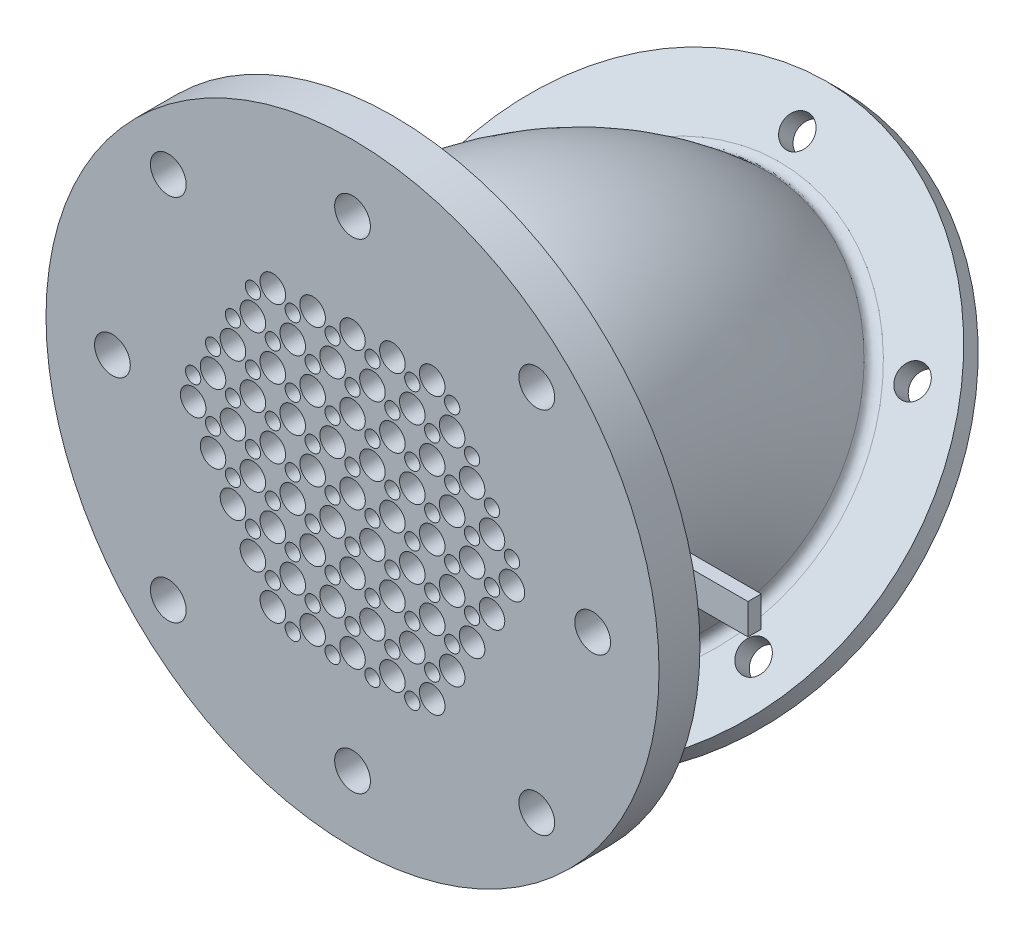
SolidWorks part; units mm, degrees
ref_plane "Спереди" through (0, 0, 0) normal (0, 0, 1) x (1, 0, 0)
ref_plane "Сверху" through (0, 0, 0) normal (0, 1, 0) x (1, 0, 0)
ref_plane "Справа" through (0, 0, 0) normal (1, 0, 0) x (0, 0, -1)
sketch "Sketch1" plane through (0, 0, 0) normal (0, 0, 1) x (1, 0, 0)
  line L0 (3.9, 6.755) -> (7.8, 0) construction
  line L2 (5.85, 10.1325) -> (11.7, 0) construction
  line L4 (7.8, 13.51) -> (15.6, 0) construction
  circle A61 centre (0, 0) radius 18.6468
  circle A131 centre (0, 0) radius 1.25
  circle A484 centre (3.9, 0) radius 1.25
  circle A485 centre (7.8, 0) radius 1.25
  circle A486 centre (11.7, 0) radius 1.25
  circle A487 centre (15.6, 0) radius 1.25
  circle A488 centre (1.95, -3.3775) radius 1.25
  circle A489 centre (3.9, -6.755) radius 1.25
  circle A490 centre (5.85, -10.1325) radius 1.25
  circle A491 centre (7.8, -13.51) radius 1.25
  circle A492 centre (-1.95, -3.3775) radius 1.25
  circle A493 centre (-3.9, -6.755) radius 1.25
  circle A494 centre (-5.85, -10.1325) radius 1.25
  circle A495 centre (-7.8, -13.51) radius 1.25
  circle A496 centre (-3.9, 0) radius 1.25
  circle A497 centre (-7.8, 0) radius 1.25
  circle A498 centre (-11.7, 0) radius 1.25
  circle A499 centre (-15.6, 0) radius 1.25
  circle A500 centre (-1.95, 3.3775) radius 1.25
  circle A501 centre (-3.9, 6.755) radius 1.25
  circle A502 centre (-5.85, 10.1325) radius 1.25
  circle A503 centre (-7.8, 13.51) radius 1.25
  circle A504 centre (1.95, 3.3775) radius 1.25
  circle A505 centre (3.9, 6.755) radius 1.25
  circle A506 centre (5.85, 10.1325) radius 1.25
  circle A507 centre (7.8, 13.51) radius 1.25
  circle A508 centre (5.85, 3.3775) radius 1.25
  circle A509 centre (7.8, 6.755) radius 1.25
  circle A510 centre (9.75, 3.3775) radius 1.25
  circle A511 centre (11.7, 6.755) radius 1.25
  circle A512 centre (9.7491, 10.1341) radius 1.25
  circle A513 centre (13.6509, 3.3759) radius 1.25
  circle A514 centre (5.85, -3.3791) radius 1.25
  circle A515 centre (9.75, -3.3791) radius 1.25
  circle A516 centre (7.8, -6.7566) radius 1.25
  circle A517 centre (11.7, -6.7566) radius 1.25
  circle A518 centre (9.7491, -10.1356) radius 1.25
  circle A519 centre (13.6509, -3.3775) radius 1.25
  circle A520 centre (-0.0013, -6.7573) radius 1.25
  circle A521 centre (1.9487, -10.1348) radius 1.25
  circle A522 centre (-1.9513, -10.1348) radius 1.25
  circle A523 centre (-0.0013, -13.5123) radius 1.25
  circle A524 centre (-3.9032, -13.5123) radius 1.25
  circle A525 centre (3.9005, -13.5123) radius 1.25
  circle A526 centre (-5.8527, -3.3791) radius 1.25
  circle A527 centre (-7.8027, -6.7566) radius 1.25
  circle A528 centre (-9.7527, -3.3791) radius 1.25
  circle A529 centre (-11.7027, -6.7566) radius 1.25
  circle A530 centre (-13.6536, -3.3775) radius 1.25
  circle A531 centre (-9.7518, -10.1356) radius 1.25
  circle A532 centre (-5.8527, 3.3775) radius 1.25
  circle A533 centre (-9.7527, 3.3775) radius 1.25
  circle A534 centre (-7.8027, 6.755) radius 1.25
  circle A535 centre (-11.7027, 6.755) radius 1.25
  circle A536 centre (-9.7518, 10.1341) radius 1.25
  circle A537 centre (-13.6536, 3.3759) radius 1.25
  circle A538 centre (-0.0014, 6.7558) radius 1.25
  circle A539 centre (-1.9514, 10.1333) radius 1.25
  circle A540 centre (1.9486, 10.1333) radius 1.25
  circle A541 centre (-0.0014, 13.5108) radius 1.25
  circle A542 centre (3.9005, 13.5108) radius 1.25
  circle A543 centre (-3.9032, 13.5108) radius 1.25
  circle A544 centre (13.65, -1.1258) radius 2.2517 construction
  circle A545 centre (11.7009, -4.5044) radius 2.2522 construction
  circle A546 centre (9.75, -7.8834) radius 2.2522 construction
  circle A547 centre (7.7987, -11.2591) radius 2.2509 construction
  circle A548 centre (13.65, -1.1258) radius 0.75
  circle A549 centre (11.7009, -4.5044) radius 0.75
  circle A550 centre (9.75, -7.8834) radius 0.75
  circle A551 centre (7.7987, -11.2591) radius 0.75
  circle A552 centre (9.75, -1.1258) radius 0.75
  circle A553 centre (7.8009, -4.5044) radius 0.75
  circle A554 centre (5.85, -7.8834) radius 0.75
  circle A555 centre (3.8987, -11.2591) radius 0.75
  circle A556 centre (5.85, -1.1258) radius 0.75
  circle A557 centre (3.9009, -4.5044) radius 0.75
  circle A558 centre (1.95, -7.8834) radius 0.75
  circle A559 centre (-0.0013, -11.2591) radius 0.75
  circle A560 centre (1.95, -1.1258) radius 0.75
  circle A561 centre (0.0009, -4.5044) radius 0.75
  circle A562 centre (-1.95, -7.8834) radius 0.75
  circle A563 centre (-3.9013, -11.2591) radius 0.75
  circle A564 centre (-1.95, -1.1258) radius 0.75
  circle A565 centre (-3.8991, -4.5044) radius 0.75
  circle A566 centre (-5.85, -7.8834) radius 0.75
  circle A567 centre (-7.8013, -11.2591) radius 0.75
  circle A568 centre (-5.85, -1.1258) radius 0.75
  circle A569 centre (-7.7991, -4.5044) radius 0.75
  circle A570 centre (-9.75, -7.8834) radius 0.75
  circle A572 centre (-9.75, -1.1258) radius 0.75
  circle A573 centre (-11.6991, -4.5044) radius 0.75
  circle A576 centre (-13.65, -1.1258) radius 0.75
  circle A580 centre (-15.5991, -4.5044) radius 0.75
  circle A581 centre (-13.65, -7.8834) radius 0.75
  circle A582 centre (-17.55, -7.8834) radius 0.75
  circle A583 centre (-19.5013, -11.2591) radius 0.75
  circle A584 centre (-15.6013, -11.2591) radius 0.75
  circle A585 centre (-11.7013, -11.2591) radius 0.75
  circle A587 centre (0, 2.2517) radius 2.2517 construction
  circle A588 centre (0, 2.2517) radius 0.75
  circle A589 centre (3.9, 2.2517) radius 0.75
  circle A590 centre (7.8, 2.2517) radius 0.75
  circle A591 centre (11.7, 2.2517) radius 0.75
  circle A592 centre (15.6, 2.2517) radius 0.75
  circle A593 centre (1.9491, 5.6297) radius 2.2522 construction
  circle A594 centre (1.9491, 5.6297) radius 0.75
  circle A595 centre (5.8491, 5.6297) radius 0.75
  circle A596 centre (9.7491, 5.6297) radius 0.75
  circle A597 centre (13.6491, 5.6297) radius 0.75
  circle A598 centre (3.8991, 9.0072) radius 2.2522 construction
  circle A599 centre (3.8991, 9.0072) radius 0.75
  circle A600 centre (7.7991, 9.0072) radius 0.75
  circle A601 centre (11.6991, 9.0072) radius 0.75
  circle A602 centre (5.85, 12.3842) radius 2.2517 construction
  circle A603 centre (5.85, 12.3842) radius 0.75
  circle A604 centre (9.75, 12.3842) radius 0.75
  circle A605 centre (5.85, -14.6358) radius 0.75
  circle A606 centre (1.9509, -14.6353) radius 0.75
  circle A607 centre (-1.9491, -14.6353) radius 0.75
  circle A608 centre (-5.85, -14.6358) radius 0.75
  circle A609 centre (-15.6, 2.2517) radius 0.75
  circle A610 centre (-13.65, 5.6281) radius 0.75
  circle A611 centre (-11.7, 9.0056) radius 0.75
  circle A612 centre (-9.75, 12.3842) radius 0.75
  circle A613 centre (-5.85, 12.3842) radius 0.75
  circle A614 centre (-1.95, 12.3842) radius 0.75
  circle A615 centre (1.95, 12.3842) radius 0.75
  circle A616 centre (-7.8, 9.0056) radius 0.75
  circle A617 centre (-9.75, 5.6281) radius 0.75
  circle A618 centre (-11.7, 2.2517) radius 0.75
  circle A619 centre (-3.9, 9.0056) radius 0.75
  circle A620 centre (-5.85, 5.6281) radius 0.75
  circle A621 centre (-7.8, 2.2517) radius 0.75
  circle A622 centre (0, 9.0056) radius 0.75
  circle A623 centre (-1.95, 5.6281) radius 0.75
  circle A624 centre (-3.9, 2.2517) radius 0.75
  point P51 (0, 0)
  point P125 (-0.0013, -0.0008)
  point P231 (0, 0)
  dimension "D1" = 5
  dimension "D3" = 6
  dimension "D5" = 8
  dimension "D7" = 4
  dimension "D2" = 6
  dimension "D6" = 5
  dimension "D8" = 3
  dimension "D9" = 2
  dimension "D4" = 1.5
  dimension "D10" = 3
sketch "Sketch2" plane through (0, 0, 0) normal (1, 0, 0) x (0, 0, -1)
  line L0 (0, 0) -> (10, 0)
  line L1 (37.4234, -27.4234) -> (37.4234, -34.4234)
  arc A0 (10, 0) -> (37.4234, -27.4234) centre (10, -27.4234) cw
  dimension "D1" = 27.4234
sketch "Sketch4" plane through (0, 0, 0) normal (1, 0, 0) x (0, 0, -1)
  line L1 (-31.2382, 44.0572) -> (87.6543, 44.0572)
  line L2 (-31.2382, 44.0572) -> (-31.2382, -52.5019)
  line L3 (-31.2382, -52.5019) -> (87.6543, -52.5019)
  line L4 (87.6543, 44.0572) -> (87.6543, -52.5019)
sweep "Sweep1" add profiles "Sketch1" path "Sketch2"
sketch "Sketch5" plane through (0, 0, 0) normal (0, 0, 1) x (1, 0, 0)
  circle A0 centre (0, 0) radius 23.5 construction
  circle A1 centre (0, 0) radius 30
  circle A2 centre (0, 0) radius 17.1737
extrude "Boss-Extrude1" add sketch "Sketch5" against normal blind 4
fillet "Fillet1" radius 2 1 edges at (18.6468, 0, -4)
sketch "Sketch6" plane through (0, 0, 0) normal (0, 0, 1) x (1, 0, 0)
  circle A0 centre (0, 0) radius 23.5 construction
  circle A2 centre (23.5, 0) radius 1.75
  circle A4 centre (0, -23.5) radius 1.75
  circle A5 centre (-23.5, 0) radius 1.75
  circle A6 centre (0, 23.5) radius 1.75
  point P14 (0, 0)
  dimension "D1" = 4
extrude "Cut-Extrude2" cut sketch "Sketch6" against normal blind 5
sketch "Sketch8" plane through (0, 0, 0) normal (0, 0, 1) x (1, 0, 0)
  line L0 (0, 0) -> (-19.915, 0)
  line L1 (0, 0) -> (-18.0312, 18.0312) construction
  circle A0 centre (0, 0) radius 25.5 construction
  circle A1 centre (-18.0312, 18.0312) radius 1.75
  circle A2 centre (18.0312, 18.0312) radius 1.75
  circle A3 centre (18.0312, -18.0312) radius 1.75
  circle A4 centre (-18.0312, -18.0312) radius 1.75
  point P15 (0, 0)
  dimension "D1" = 4
extrude "Cut-Extrude3" cut sketch "Sketch8" against normal blind 5 contours A2 | A1 | A4 | A3
sketch "Sketch9" plane through (0, 0, 0) normal (1, 0, 0) x (0, 0, -1)
  line L0 (16.206, -21.2174) -> (45.1688, 7.7454) construction
  arc A0 (18.7766, -27.4234) -> (10, -18.6468) centre (10, -27.4234) ccw construction
ref_plane "Plane1" through (0, -18.7117, -18.7117) normal (0, 0.7071, 0.7071) x (0, 0.7071, -0.7071)
sketch "Sketch10" plane through (0, -18.7117, -18.7117) normal (0, 0.7071, 0.7071) x (0, 0.7071, -0.7071)
  line L1 (-46.7536, 40.8154) -> (60.8519, 40.8154)
  line L2 (-46.7536, 40.8154) -> (-46.7536, -39.2382)
  line L3 (-46.7536, -39.2382) -> (60.8519, -39.2382)
  line L4 (60.8519, 40.8154) -> (60.8519, -39.2382)
extrude "Cut-Extrude4" cut sketch "Sketch10" against normal blind 50
sketch "Sketch12" plane through (0, 0, 0) normal (0, 1, 0) x (1, 0, 0)
  line L0 (18.6468, 10) -> (-18.6468, 10) construction
  line L1 (17.7467, 10) -> (30, 10)
  line L2 (17.7467, 10) -> (17.7467, 8.7)
  line L3 (17.7467, 8.7) -> (30, 8.7)
  line L4 (30, 10) -> (30, 8.7)
extrude "Boss-Extrude3" add sketch "Sketch12" along normal mid plane 3
sketch "Sketch15" plane through (0, -18.7117, -18.7117) normal (0, -0.7071, -0.7071) x (1, 0, 0)
  circle A2 centre (0, -15.1032) radius 26
  circle A4 centre (0, -15.1032) radius 17.5906
extrude "Boss-Extrude6" add sketch "Sketch15" against normal blind 2
sketch "Sketch16" plane through (0, -18.7117, -18.7117) normal (0, -0.7071, -0.7071) x (-1, 0, 0)
  circle A0 centre (0, 15.1032) radius 22 construction
  circle A1 centre (0, -6.8968) radius 1.5
  circle A2 centre (0, 37.1032) radius 1.5
  circle A3 centre (19.0526, 4.1032) radius 1.5
  circle A4 centre (-19.0526, 26.1032) radius 1.5
  circle A5 centre (0, 15.1032) radius 22 construction
  circle A6 centre (-19.0526, 4.1032) radius 1.5
  circle A7 centre (19.0526, 26.1032) radius 1.5
  circle A8 centre (0, 15.1032) radius 22 construction
  point P18 (0, 15.1032)
  dimension "D1" = 3
  dimension "D2" = 44
extrude "Cut-Extrude5" cut sketch "Sketch16" against normal blind 2
fillet "Fillet2" radius 1 1 edges at (17.8758, -10.4343, -24.1606)
